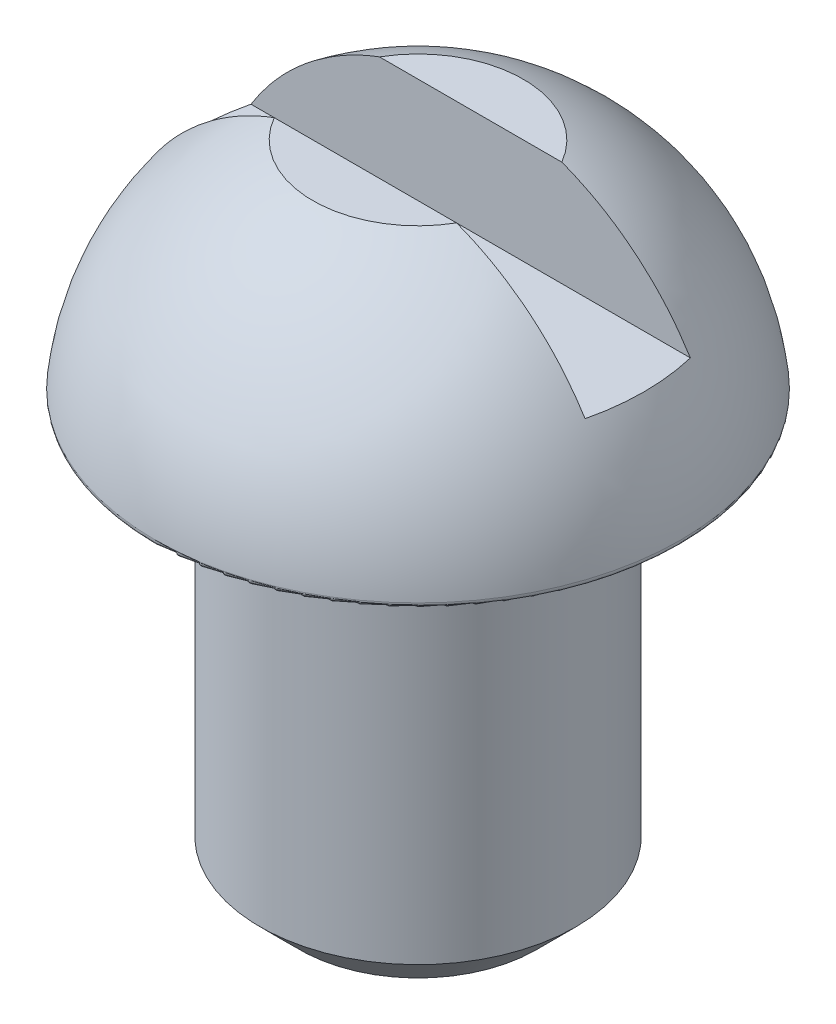
SolidWorks part; units mm, degrees
ref_plane "Спереди" through (0, 0, 0) normal (0, 0, 1) x (1, 0, 0)
ref_plane "Сверху" through (0, 0, 0) normal (0, 1, 0) x (1, 0, 0)
ref_plane "Справа" through (0, 0, 0) normal (1, 0, 0) x (0, 0, -1)
sketch "Эскиз1" plane through (0, 0, 0) normal (0, 0, 1) x (1, 0, 0)
  line L0 (5, 8) -> (3, 8)
  line L1 (0, 0) -> (0, 12.2)
  line L2 (3, 8) -> (3, 0.75)
  line L3 (3, 0.75) -> (2.25, 0)
  line L4 (2.25, 0) -> (0, 0)
  line L5 (0, 12.2) -> (2, 12.2)
  arc A0 (2, 12.2) -> (5, 8) centre (0.0152, 7.6108) cw
  point P9 (0, 0)
  dimension "D2" = 2
  dimension "D3" = 5
  dimension "D1" = 8
  dimension "D4" = 2.25
  dimension "D5" = 4.2
  dimension "D6" = 5
  dimension "D7" = 45
  dimension "D9" = 3
revolve "Повернуть1" add sketch "Эскиз1" angle 360 about L1
fillet "Скругление1" radius 0.1 1 edges at (5, 8, 0)
sketch "Эскиз3" plane through (0, 12.2, 0) normal (0, 1, 0) x (-1, 0, 0)
  line L1 (5, -1) -> (-5, -1)
  line L2 (5, -1) -> (5, 1)
  line L3 (5, 1) -> (-5, 1)
  line L4 (-5, -1) -> (-5, 1)
  dimension "D1" = 2
  dimension "D2" = 1
  dimension "D3" = 10
  dimension "D4" = 5
extrude "Вырез-Вытянуть2" cut sketch "Эскиз3" against normal blind 2
ref_axis "Ось1" through (0, -104.1565, 0) along (0, 1, 0)
